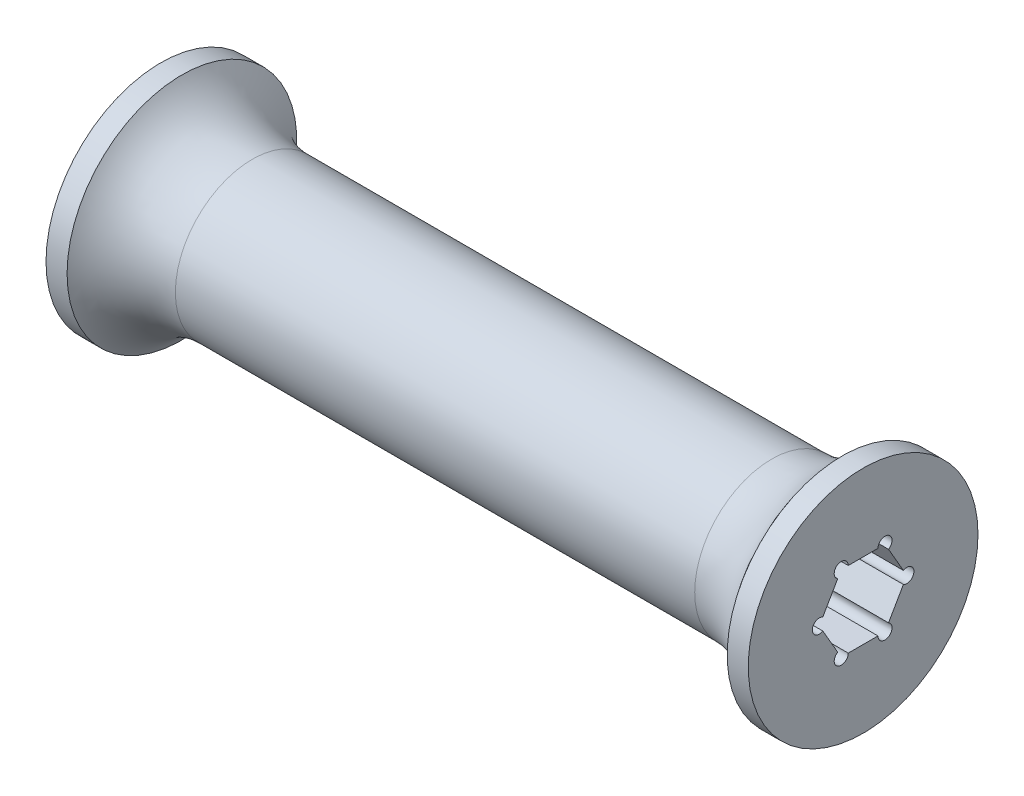
SolidWorks part; units mm, degrees
ref_plane "Front Plane" through (0, 0, 0) normal (0, 0, 1) x (1, 0, 0)
ref_plane "Top Plane" through (0, 0, 0) normal (0, 1, 0) x (1, 0, 0)
ref_plane "Right Plane" through (0, 0, 0) normal (1, 0, 0) x (0, 0, -1)
sketch "Sketch1" plane through (0, 0, 0) normal (1, 0, 0) x (0, 0, -1)
  arc A3 (364.5277, 95.1985) -> (364.4523, 67.3615) centre (364.49, 81.28) ccw construction
  circle A8 centre (364.49, 81.28) radius 13.9186
extrude "Boss-Extrude1" add sketch "Sketch1" along normal mid plane 127
sketch "Sketch3" plane through (-63.5, 0, 0) normal (-1, 0, 0) x (0, 0, 1)
  circle A0 centre (-364.49, 81.28) radius 20.7766
  circle A1 centre (-364.49, 81.28) radius 13.9186
  circle A2 centre (-364.49, 81.28) radius 13.9186 construction
  dimension "D1" = 6.858
extrude "Boss-Extrude2" add sketch "Sketch3" against normal blind 3.81
fillet "Fillet1" radius 15.24 1 edges at (-59.69, 81.28, -350.5714)
sketch "Sketch4" plane through (63.5, 0, 0) normal (1, 0, 0) x (0, 0, -1)
  circle A0 centre (364.49, 81.28) radius 13.9186
  circle A1 centre (364.49, 81.28) radius 20.7766
  circle A2 centre (364.49, 81.28) radius 13.9186 construction
  dimension "D1" = 6.858
extrude "Boss-Extrude3" add sketch "Sketch4" against normal blind 3.81
fillet "Fillet2" radius 15.24 1 edges at (59.69, 81.28, -378.4086)
sketch "Sketch5" plane through (63.5, 0, 0) normal (1, 0, 0) x (0, 0, -1)
  circle A0 centre (364.49, 81.28) radius 14.3129
  circle A1 centre (364.49, 81.28) radius 20.7766 construction
  dimension "D1" = 28.6258
sketch "Sketch6" plane through (-63.5, 0, 0) normal (-1, 0, 0) x (0, 0, 1)
  circle A0 centre (-364.49, 81.28) radius 14.3256
  circle A1 centre (-364.49, 81.28) radius 20.7766 construction
  dimension "D1" = 28.6512
sketch "Sketch7" plane through (63.5, 0, 0) normal (1, 0, 0) x (0, 0, -1)
  line L1 (372.4089, 81.28) -> (368.4495, 88.138)
  line L2 (368.4495, 88.138) -> (360.5305, 88.138)
  line L3 (360.5305, 88.138) -> (356.5711, 81.28)
  line L4 (356.5711, 81.28) -> (360.5305, 74.422)
  line L5 (360.5305, 74.422) -> (368.4495, 74.422)
  line L6 (368.4495, 74.422) -> (372.4089, 81.28)
  circle A0 centre (364.49, 81.28) radius 6.858 construction
  circle A1 centre (360.5305, 88.138) radius 1.27
  circle A2 centre (368.4495, 88.138) radius 1.27
  circle A3 centre (356.5711, 81.28) radius 1.27
  circle A4 centre (360.5305, 74.422) radius 1.27
  circle A5 centre (368.4495, 74.422) radius 1.27
  circle A6 centre (372.4089, 81.28) radius 1.27
  dimension "D1" = 13.716
  dimension "D2" = 2.54
extrude "Cut-Extrude1" cut sketch "Sketch7" against normal through all contours A6 L1 A2 L2 A1 L3 A3 L4 A4 L5 A5 L6 | L3 A1 L2 | L2 A1 L3 | L4 A3 L3 | L3 A3 L4 | L5 A4 L4 | L4 A4 L5 | L2 A2 L1 | L1 A2 L2 | L6 A6 L1 | L1 A6 L6 | L6 A5 L5 | L5 A5 L6 region at (63.5, 81.28, -371.7087) region at (63.5, 81.28, -372.759) region at (63.5, 81.28, -364.49) region at (63.5, 87.5316, -368.0994) region at (63.5, 88.4412, -368.6245) region at (63.5, 74.1188, -368.6245) region at (63.5, 75.0284, -368.0994) region at (63.5, 87.5316, -360.8806) region at (63.5, 88.4412, -360.3555) region at (63.5, 74.1188, -360.3555) region at (63.5, 75.0284, -360.8806) region at (63.5, 81.28, -357.2713) region at (63.5, 81.28, -356.221)
